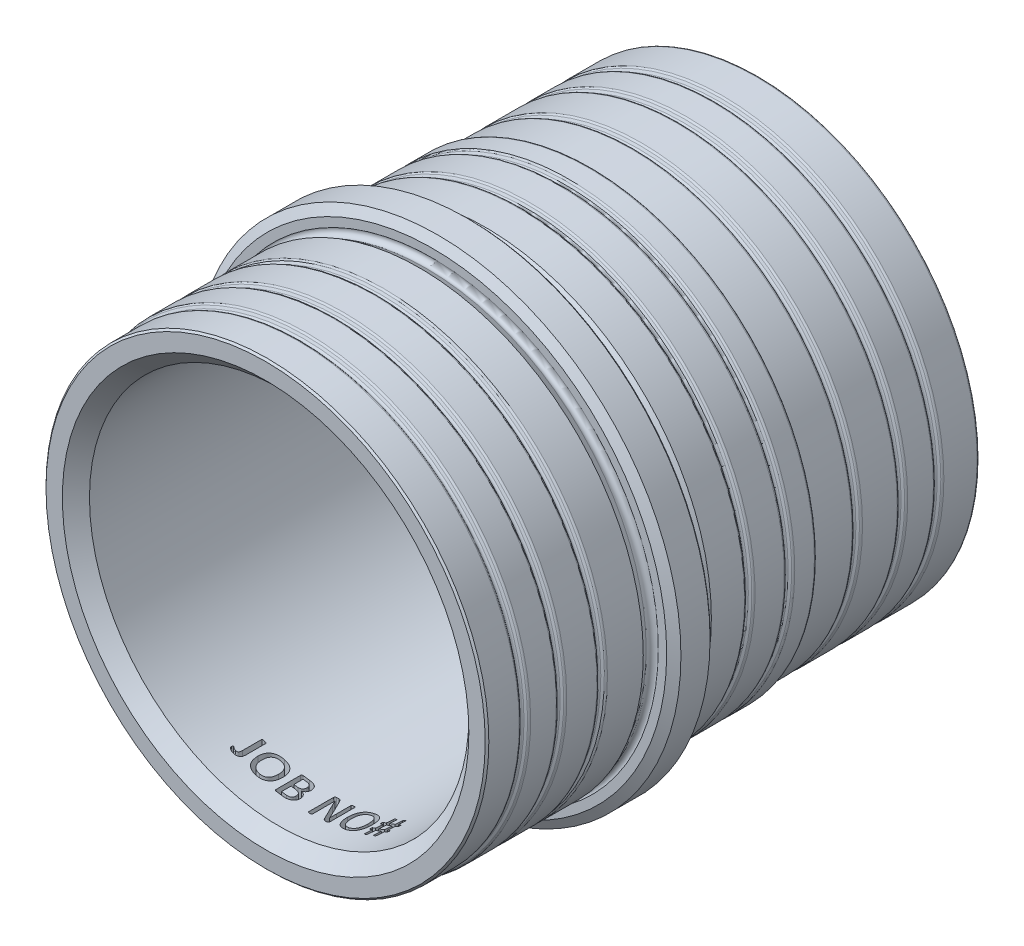
SolidWorks part; units mm, degrees
ref_plane "Front Plane" through (0, 0, 0) normal (0, 0, 1) x (1, 0, 0)
ref_plane "Top Plane" through (0, 0, 0) normal (0, 1, 0) x (1, 0, 0)
ref_plane "Right Plane" through (0, 0, 0) normal (1, 0, 0) x (0, 0, -1)
sketch "Sketch1" plane through (0, 0, 0) normal (1, 0, 0) x (0, 0, -1)
  line L0 (0, 0) -> (54.5, 0) construction
  line L1 (1.5, 20.99) -> (53, 20.99)
  line L4 (54.5, 24.475) -> (36, 24.475)
  line L5 (36, 24.475) -> (36, 24.975)
  line L6 (36, 24.975) -> (22.5, 24.975)
  line L7 (22.5, 24.975) -> (22.5, 26.68)
  line L8 (22.3, 26.88) -> (18.5, 26.88)
  line L9 (18.5, 26.88) -> (18.5, 24.75)
  line L10 (18.5, 24.75) -> (4.0521, 24.75)
  line L11 (0, 24.5) -> (0, 22.49)
  line L12 (54.5, 24.475) -> (54.5, 22.49)
  line L13 (19.0774, 26.88) -> (18.5, 25.88)
  line L14 (4.0521, 24.75) -> (4.0521, 24.5)
  line L15 (4.0521, 24.5) -> (0, 24.5)
  line L16 (0, 22.49) -> (1.5, 20.99)
  line L17 (54.5, 22.49) -> (53, 20.99)
  line L18 (22.3, 26.88) -> (22.5, 26.68)
  point P17 (22.5, 26.88)
  dimension "D12" = 0.2
  dimension "D1" = 48.95
  dimension "D2" = 49.95
  dimension "D3" = 53.76
  dimension "D4" = 49.5
  dimension "D5" = 41.98
  dimension "D6" = 1.5
  dimension "D7" = 32
  dimension "D8" = 4
  dimension "D9" = 18.5
  dimension "D10" = 1
  dimension "D11" = 30
  dimension "D13" = 49
  dimension "D14" = 4.0521
  dimension "D15" = 0.2
  dimension "D16" = 18.5
revolve "Revolve1" add sketch "Sketch1" angle 360 about L0
sketch "Sketch2" plane through (0, 0, 0) normal (1, 0, 0) x (0, 0, -1)
  line L0 (0, 0) -> (54.5, 0) construction
  line L1 (0, 24.75) -> (0, -24.75) construction
  line L2 (54.5, -24.475) -> (54.5, 24.475) construction
  line L3 (49.7835, 24.1) -> (49.567, 24.475)
  line L4 (54.5, 24.475) -> (36, 24.475) construction
  line L5 (50, 24.6923) -> (50, 23.975) construction
  line L6 (50.2165, 24.1) -> (50.433, 24.475)
  line L8 (54.5, 24.475) -> (36, 24.475) construction
  arc A0 (49.7835, 24.1) -> (50.2165, 24.1) centre (50, 24.225) ccw
  arc A1 (49.567, 24.475) -> (50.433, 24.475) centre (50, 24.1523) cw
  dimension "D1" = 0.5
  dimension "D2" = 0.5
  dimension "D3" = 30
  dimension "D4" = 4.5
revolve "Cut-Revolve1" cut sketch "Sketch2" angle 360 about L0
pattern_linear "LPattern1" count 2 spacing 4 along (0, 0, 1) of "Cut-Revolve1"
pattern_linear "LPattern2" count 2 spacing 9 along (0, 0, 1) of "Cut-Revolve1"
sketch "Sketch3" plane through (0, 0, 0) normal (1, 0, 0) x (0, 0, -1)
  line L1 (33, 25.116) -> (33, 24.475) construction
  line L2 (32.7835, 24.6) -> (32.567, 24.975)
  line L3 (33.2165, 24.6) -> (33.433, 24.975)
  line L4 (36, 24.975) -> (33.433, 24.975) construction
  line L5 (36, -24.975) -> (36, 24.975) construction
  line L6 (36, 24.975) -> (22.5, 24.975) construction
  line L7 (0, 0) -> (54.5, 0) construction
  line L8 (54.5, -24.475) -> (54.5, 24.475) construction
  arc A0 (32.7835, 24.6) -> (33.2165, 24.6) centre (33, 24.725) ccw
  arc A1 (32.567, 24.975) -> (33.433, 24.975) centre (33, 24.3805) cw
  dimension "D1" = 0.5
  dimension "D2" = 0.5
  dimension "D3" = 30
  dimension "D4" = 3
revolve "Cut-Revolve2" cut sketch "Sketch3" angle 360 about L7
pattern_linear "LPattern3" count 2 spacing 4.4 along (0, 0, 1) of "Cut-Revolve2"
sketch "Sketch4" plane through (0, 0, 0) normal (1, 0, 0) x (0, 0, -1)
  line L0 (0, 0) -> (54.5, 0) construction
  line L1 (54.5, -24.475) -> (54.5, 24.475) construction
  line L2 (28.167, 24.975) -> (28.167, -24.975) construction
  line L3 (28.167, 24.975) -> (28.167, -24.975) construction
  line L5 (23.21, 24.317) -> (24.3497, 24.975)
  line L6 (24.3497, 24.975) -> (24.3497, 25.3771)
  line L7 (24.3497, 25.3771) -> (22.5, 25.3771)
  line L8 (22.5, -26.88) -> (22.5, 26.88) construction
  line L10 (22.5, 24.946) -> (22.5, 25.3771)
  line L11 (22.5, -26.68) -> (22.5, 26.68) construction
  line L12 (0, 24.25) -> (54.5, 24.25) construction
  arc A1 (22.5, 24.946) -> (23.21, 24.317) centre (22.96, 24.75) ccw
  point P1 (0, 0)
  point P9 (0, 0)
  point P18 (0, 0)
  point P20 (0, 0)
  point P21 (0, 0)
  point P22 (0, 0)
  point P23 (24.2185, 24.975)
  dimension "D1" = 0.5
  dimension "D5" = 24.25
  dimension "D6" = 0
  dimension "D2" = 0.04
  dimension "D3" = 30
revolve "Cut-Revolve3" cut sketch "Sketch4" angle 360 about L0
ref_plane "Plane1" through (0, 0, -20.5) normal (0, 0, 1) x (1, 0, 0)
mirror "Mirror1" about plane through (0, 0, -20.5) normal (0, 0, 1) of "Cut-Revolve3"
sketch "Sketch5" plane through (0, 0, 0) normal (1, 0, 0) x (0, 0, -1)
  line L0 (12.5, 24.9294) -> (12.5, 24.25) construction
  line L1 (0, 0) -> (54.5, 0) construction
  line L2 (54.5, -24.475) -> (54.5, 24.475) construction
  line L3 (0, 24.5) -> (0, -24.5) construction
  line L4 (12.2835, 24.375) -> (12.067, 24.75)
  line L5 (17.04, 24.75) -> (4.0521, 24.75) construction
  line L6 (12.7165, 24.375) -> (12.933, 24.75)
  arc A0 (12.2835, 24.375) -> (12.7165, 24.375) centre (12.5, 24.5) ccw
  arc A1 (12.067, 24.75) -> (12.933, 24.75) centre (12.5, 24.317) cw
  dimension "D1" = 0.5
  dimension "D3" = 12.5
  dimension "D2" = 48.5
  dimension "D4" = 30
revolve "Cut-Revolve4" cut sketch "Sketch5" angle 360 about L1
pattern_linear "LPattern4" count 2 spacing 4.5 along (0, 0, 1) of "Cut-Revolve4"
pattern_linear "LPattern5" count 2 spacing 8.5 along (0, 0, 1) of "Cut-Revolve4"
chamfer "Chamfer1" distance 0.2 angle 45 1 edges at (24.5, 0, 0)
sketch "Sketch6" plane through (0, 0, 0) normal (0, 1, 0) x (1, 0, 0)
  line L0 (-12.5, 4.433) -> (12.5, 4.433) construction
  line L1 (24.75, 4.433) -> (-24.75, 4.433) construction
  text T0 "JOB NO#" font "Calibri" height 3
  point P4 (0, 4.433)
  dimension "D1" = 4.5
  dimension "D2" = 25
extrude "Cut-Extrude1" cut sketch "Sketch6" against normal blind 22
ref_plane "Plane2" through (0, 0, -1.5) normal (0, 0, 1) x (1, 0, 0)
fillet "Fillet1" radius 0.25 2 edges at (24.475, 0, -54.5) (24.475, 0, -36)
fillet "Fillet2" radius 0.25 1 edges at (24.975, 0, -36)
fillet "Fillet3" radius 0.25 1 edges at (0, -24.75, -4.433)
fillet "Fillet4" radius 0.25 15 edges at (0, -24.5, -3.7113) (0, -24.75, -7.567) (0, -24.75, -8.433) (0, -24.75, -12.067) (0, -24.75, -12.933) (24.975, 0, -28.167) (24.975, 0, -29.033) (24.975, 0, -32.567) (24.975, 0, -33.433) (24.475, 0, -40.567) (24.475, 0, -41.433) (24.475, 0, -45.567) (24.475, 0, -46.433) (24.475, 0, -49.567) (24.475, 0, -50.433)
